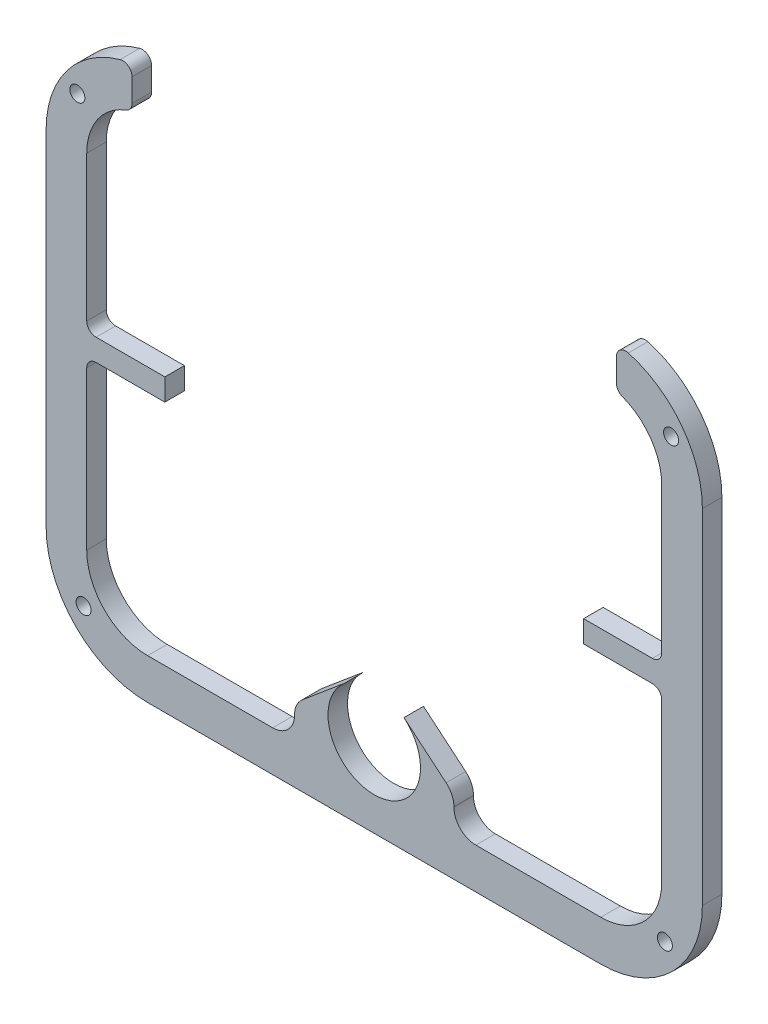
SolidWorks part; units mm, degrees
material "Delrin 2700 NC010, Low Viscosity Acetal Copolymer (SS)"
ref_plane "Front Plane" through (0, 0, 0) normal (0, 0, 1) x (1, 0, 0)
ref_plane "Top Plane" through (0, 0, 0) normal (0, 1, 0) x (1, 0, 0)
ref_plane "Right Plane" through (0, 0, 0) normal (1, 0, 0) x (0, 0, -1)
sketch "Sketch1" plane through (0, 0, 0) normal (0, 0, 1) x (1, 0, 0)
  line L0 (-18.415, -18.923) -> (-9.6321, -18.923)
  line L1 (18.415, 22.225) -> (-18.415, 22.225)
  line L2 (26.67, 13.97) -> (26.67, -13.97)
  line L3 (18.415, -22.225) -> (-18.415, -22.225)
  line L4 (-26.67, 13.97) -> (-26.67, -13.97)
  line L5 (26.67, 22.225) -> (-26.67, -22.225) construction
  line L6 (26.67, -22.225) -> (-26.67, 22.225) construction
  line L7 (9.6321, -18.923) -> (18.415, -18.923)
  line L8 (-23.368, -0.381) -> (-17.018, -0.381)
  line L9 (23.368, 1.397) -> (17.018, 1.397)
  line L10 (-23.368, 13.97) -> (-23.368, -13.97)
  line L11 (-1000, 0) -> (49000, 0) construction
  line L12 (-23.368, 0) -> (-23.368, -1.27)
  line L13 (23.368, 13.97) -> (23.368, -13.97)
  line L14 (18.415, 18.923) -> (-18.415, 18.923)
  line L15 (23.368, 1.397) -> (23.368, -0.381)
  line L16 (23.368, -0.381) -> (17.018, -0.381)
  line L17 (17.018, 1.397) -> (17.018, -0.381)
  line L18 (0, 18.923) -> (0, -18.415) construction
  line L19 (-17.018, 1.397) -> (-17.018, -0.381)
  line L20 (-23.368, 1.397) -> (-17.018, 1.397)
  line L21 (2.4164, -12.8683) -> (9.6321, -18.923)
  line L22 (-2.4164, -12.8683) -> (-9.6321, -18.923)
  line L36 (18.415, -18.923) -> (-18.415, -18.923) construction
  arc A0 (-2.4164, -12.8683) -> (2.4164, -12.8683) centre (0, -15.748) ccw
  arc A1 (-18.415, 22.225) -> (-26.67, 13.97) centre (-18.415, 13.97) ccw
  arc A2 (18.415, 22.225) -> (26.67, 13.97) centre (18.415, 13.97) cw
  arc A3 (26.67, -13.97) -> (18.415, -22.225) centre (18.415, -13.97) cw
  arc A4 (-18.415, -22.225) -> (-26.67, -13.97) centre (-18.415, -13.97) cw
  arc A7 (18.415, 18.923) -> (23.368, 13.97) centre (18.415, 13.97) cw
  arc A8 (-18.415, 18.923) -> (-23.368, 13.97) centre (-18.415, 13.97) ccw
  arc A13 (-18.415, -18.923) -> (-23.368, -13.97) centre (-18.415, -13.97) cw construction
  arc A14 (23.368, -13.97) -> (18.415, -18.923) centre (18.415, -13.97) cw construction
  arc A15 (-23.368, -13.97) -> (-18.415, -18.923) centre (-18.415, -13.97) ccw
  arc A16 (18.415, -18.923) -> (23.368, -13.97) centre (18.415, -13.97) ccw
  point P0 (0, 0)
  dimension "D4" = 7.5184
  dimension "D6" = 8.255
  dimension "D7" = 8.255
  dimension "D8" = 8.255
  dimension "D9" = 8.255
  dimension "D1" = 53.34
  dimension "D2" = 44.45
  dimension "D10" = 3.302
  dimension "D3" = 3.175
  dimension "D13" = 15.748
  dimension "D14" = 1.778
  dimension "D15" = 21.844
  dimension "D16" = 6.35
extrude "Boss-Extrude1" add sketch "Sketch1" along normal blind 1.5875 contours A4 L3 A3 L2 A2 L1 A1 L4 A16 L7 L21 A0 L22 L0 A15 L10 A8 L14 A7 L13 | L9 L17 L16 L13 | L20 L10 L8 L19 region at (-20.193, 0.508, 0) region at (20.193, 0.508, 0) region at (23.7612, 19.3162, 0)
sketch "Sketch2" plane through (0, 0, 1.5875) normal (0, 0, 1) x (1, 0, 0)
  line L1 (-9.6321, -18.923) -> (-6.477, -18.923)
  line L2 (-9.6321, -18.923) -> (-9.6321, -16.2756)
  line L3 (-9.6321, -16.2756) -> (-6.477, -16.2756)
  line L4 (-6.477, -18.923) -> (-6.477, -16.2756)
  line L5 (0, -1000) -> (0, 49000) construction
  line L6 (9.6321, -18.923) -> (9.6321, -16.2756)
  line L7 (9.6321, -16.2756) -> (6.477, -16.2756)
  line L8 (6.477, -18.923) -> (6.477, -16.2756)
  line L9 (9.6321, -18.923) -> (6.477, -18.923)
  line L11 (-18.415, 18.923) -> (18.415, 18.923)
  line L12 (-19.685, 18.7574) -> (-19.685, 22.225)
  line L13 (-19.685, 22.225) -> (19.685, 22.225)
  line L14 (19.685, 18.7574) -> (19.685, 22.225)
  line L16 (18.415, 18.923) -> (-18.415, 18.923) construction
  line L17 (-2.4164, -12.8683) -> (-9.6321, -18.923) construction
  line L18 (18.415, 22.225) -> (-18.415, 22.225) construction
  arc A0 (23.368, 13.97) -> (18.415, 18.923) centre (18.415, 13.97) ccw construction
  arc A1 (-18.415, 18.923) -> (-23.368, 13.97) centre (-18.415, 13.97) ccw construction
  arc A2 (19.685, 18.7574) -> (18.415, 18.923) centre (18.415, 13.97) ccw
  arc A3 (-18.415, 18.923) -> (-19.685, 18.7574) centre (-18.415, 13.97) ccw
  point P25 (0, 22.225)
  dimension "D1" = 6.477
  dimension "D2" = 39.37
extrude "Cut-Extrude1" cut sketch "Sketch2" against normal up to next
fillet "Fillet1" radius 1.778 4 edges at (6.477, -18.923, 0.7937) (6.477, -16.2756, 0.7937) (-6.477, -18.923, 0.7937) (-6.477, -16.2756, 0.7937)
fillet "Fillet2" radius 0.762 4 edges at (19.685, 22.1267, 0.7937) (19.685, 18.7574, 0.7937) (-19.685, 18.7574, 0.7937) (-19.685, 22.1267, 0.7937)
fillet "Fillet3" radius 0.762 4 edges at (-23.368, -0.381, 0.7937) (23.368, -0.381, 0.7937) (23.368, 1.397, 0.7937) (-23.368, 1.397, 0.7937)
sketch "Sketch3" plane through (0, 0, 1.5875) normal (0, 0, 1) x (1, 0, 0)
  circle A0 centre (-22.86, -16.51) radius 0.6096 construction
  circle A1 centre (-22.86, 16.256) radius 0.6096 construction
  circle A2 centre (22.86, 16.256) radius 0.6096 construction
  circle A3 centre (22.86, -16.51) radius 0.6096 construction
  circle A4 centre (-22.86, -16.51) radius 0.6096 construction
  circle A5 centre (-22.86, 16.256) radius 0.6096 construction
  circle A6 centre (22.86, 16.256) radius 0.6096 construction
  circle A7 centre (22.86, -16.51) radius 0.6096 construction
  circle A8 centre (-24.13, 17.78) radius 0.6096
  circle A9 centre (-23.622, -18.034) radius 0.6096
  circle A10 centre (24.13, 17.78) radius 0.6096
  circle A11 centre (23.622, -18.034) radius 0.6096
  dimension "D1" = 1.524
  dimension "D2" = 1.27
  dimension "D3" = 1.524
  dimension "D4" = 0.762
  dimension "D5" = 1.27
  dimension "D6" = 0.762
extrude "Cut-Extrude2" cut sketch "Sketch3" against normal up to surface (1.5875 mm away) up to face at (0, -2.0741, 0)
